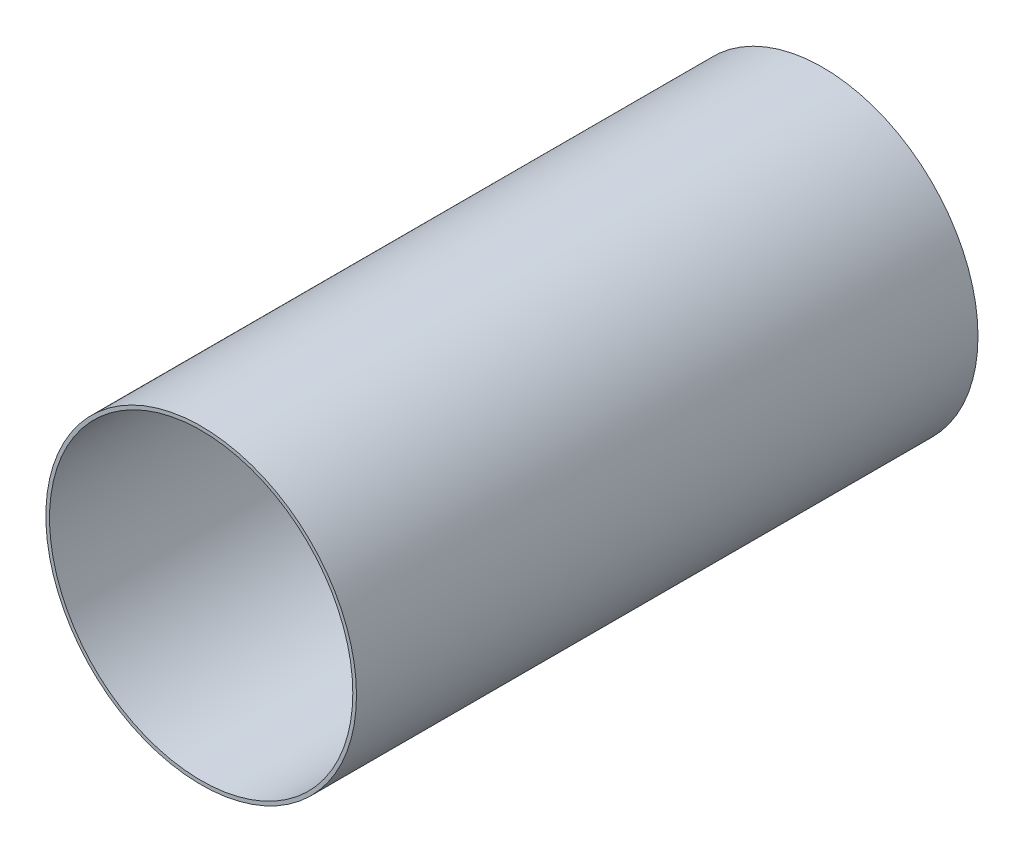
SolidWorks part; units mm, degrees
ref_plane "Front Plane" through (0, 0, 0) normal (0, 0, 1) x (1, 0, 0)
ref_plane "Top Plane" through (0, 0, 0) normal (0, 1, 0) x (1, 0, 0)
ref_plane "Right Plane" through (0, 0, 0) normal (1, 0, 0) x (0, 0, -1)
sketch "Sketch1" plane through (0, 0, 0) normal (0, 0, 1) x (1, 0, 0)
  circle A0 centre (0, 0) radius 63.4746
  circle A1 centre (0, 0) radius 61.976
  dimension "D1" = 123.952
  dimension "D2" = 126.9492
extrude "Boss-Extrude1" add sketch "Sketch1" along normal mid plane 254
equation "\"AIRFRAME_OD\"= 5.15in"
equation "\"AIRFRAME_ID\"= 5.00in"
equation "\"FLAT_T\"= 0.125in"
equation "\"NOSE_EXP_L\"= 27in"
equation "\"NOSE_SHOULDER_L\"= 5in"
equation "\"MAIN_L\"= 30in"
equation "\"RECO_COUP_L\"= 10in"
equation "\"RECO_SWITCH_L\"= 2in"
equation "\"DROGUE_L\"= 20in"
equation "\"ATS_FORE_COUP_L\"= 5.5in"
equation "\"ATS_AFT_COUP_L\"= 4.5in"
equation "\"LOWER_L\"= 30in"
equation "\"FIN_N\"= 4"
equation "\"CR_AFT_X\"= 0.5in"
equation "\"CR_FORE_X\"= 9.25in"
equation "\"D1@Sketch1\"=\"COUPLER_ID\""
equation "\"D2@Sketch1\"=\"COUPLER_OD\""
equation "\"D1@Boss-Extrude1\"=\"RECO_COUP_L\""
equation "\"FIN_ROOT\"= 5in"
equation "\"FIN_X\"= 0.75in"
equation "\"MOTOR_OD\"= 3.091in"
equation "\"MOTOR_ID\"= 3.00in"
equation "\"COUPLER_OD\"= 4.998in"
equation "\"COUPLER_ID\"= 4.88in"
equation "\"RECO_ROD_X\"= 3.5in"
equation "\"ATS_ROD_X\"= 3in"
equation "\"MOTOR_L\"= 14in"
equation "\"MOTOR_LOWER_X\"= 2in"
